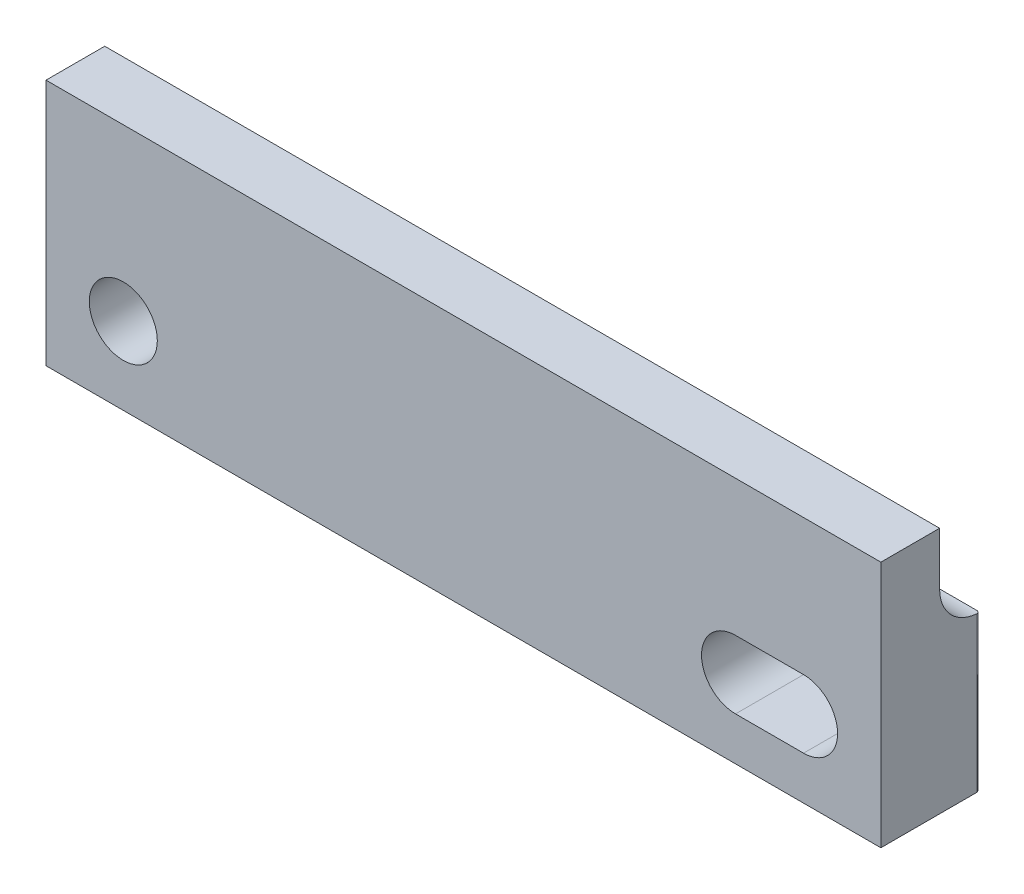
SolidWorks part; units mm, degrees
ref_plane "前视基准面" through (0, 0, 0) normal (0, 0, 1) x (1, 0, 0)
ref_plane "上视基准面" through (0, 0, 0) normal (0, 1, 0) x (1, 0, 0)
ref_plane "右视基准面" through (0, 0, 0) normal (1, 0, 0) x (0, 0, -1)
sketch "草图1" plane through (0, 0, 0) normal (0, 0, 1) x (1, 0, 0)
  line L1 (0, 0) -> (270, 0)
  line L2 (0, 0) -> (0, 80)
  line L3 (0, 80) -> (270, 80)
  line L4 (270, 0) -> (270, 80)
  dimension "D1" = 270
  dimension "D2" = 80
extrude "拉伸1" add sketch "草图1" along normal blind 32
sketch "草图2" plane through (0, 0, 32) normal (0, 0, 1) x (1, 0, 0)
  line L0 (0, 80) -> (0, 0) construction
  line L1 (0, 0) -> (270, 0) construction
  line L2 (245, -928.2855) -> (245, 49071.7145) construction
  line L3 (223, -932.4386) -> (223, 49067.5614) construction
  line L4 (270, 0) -> (270, 80) construction
  line L5 (-977.8887, 25) -> (49022.1113, 25) construction
  line L6 (223, 36) -> (245, 36)
  line L7 (223, 14) -> (245, 14)
  circle A0 centre (25, 25) radius 11
  arc A1 (223, 14) -> (223, 36) centre (223, 25) cw
  arc A2 (245, 36) -> (245, 14) centre (245, 25) cw
  dimension "D1" = 25
  dimension "D2" = 25
  dimension "D3" = 25
  dimension "D4" = 22
extrude "切除-拉伸1" cut sketch "草图2" against normal through all
sketch "草图3" plane through (0, 0, 0) normal (-1, 0, 0) x (0, 0, 1)
  line L0 (13, 80) -> (13, 63)
  line L1 (0, 80) -> (0, 0) construction
  line L3 (32, 80) -> (0, 80) construction
  line L4 (13, 80) -> (0, 80)
  line L5 (0, 80) -> (0, 50)
  arc A0 (13, 63) -> (0, 50) centre (0, 63) cw
  point P4 (0, 63)
  dimension "D1" = 17
  dimension "D2" = 13
  dimension "D3" = 13
extrude "切除-拉伸2" cut sketch "草图3" against normal through all
fillet "圆角1" radius 1 1 edges at (270, 25, 0)
fillet "圆角2" radius 1 1 edges at (0, 25, 0)
fillet "圆角4" radius 1 1 edges at (135, 0, 0) tangent propagation no
